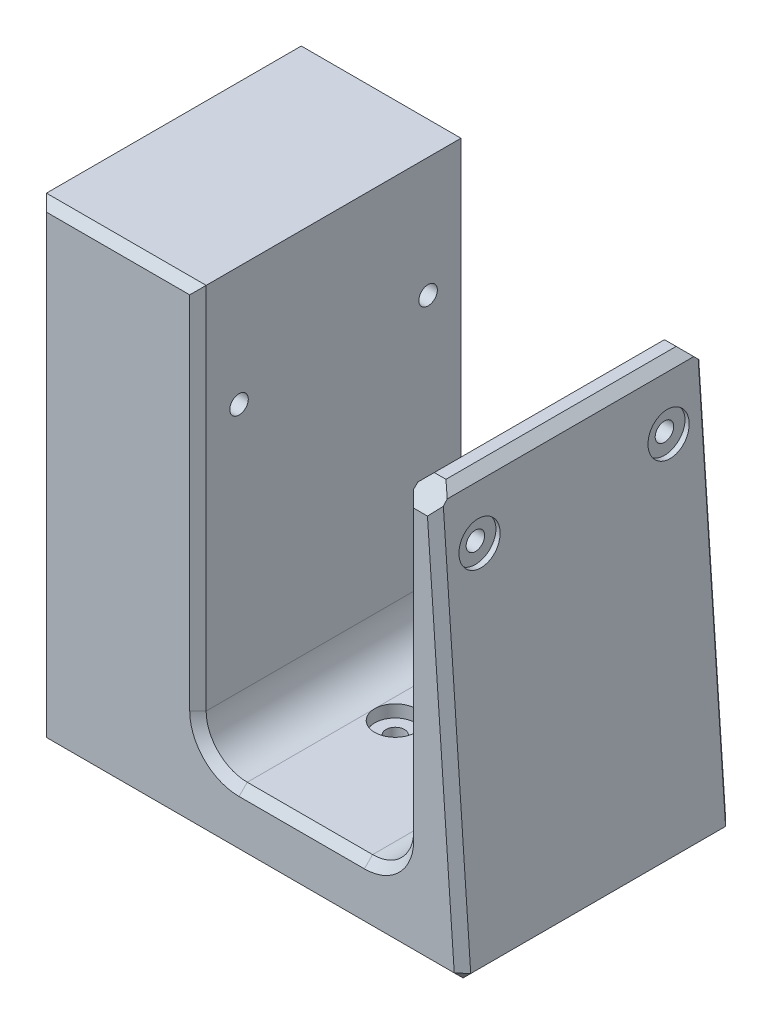
SolidWorks part; units mm, degrees
material "ABS generico"
ref_plane "Piano frontale" through (0, 0, 0) normal (0, 0, 1) x (1, 0, 0)
ref_plane "Piano superiore" through (0, 0, 0) normal (0, 1, 0) x (1, 0, 0)
ref_plane "Piano destro" through (0, 0, 0) normal (1, 0, 0) x (0, 0, -1)
sketch "Schizzo1" plane through (0, 0, 0) normal (0, 0, 1) x (1, 0, 0)
  line L0 (25.25, 100) -> (32.25, 100)
  line L1 (32.25, 100) -> (39.25, 0)
  line L2 (39.25, 0) -> (-39.25, 0)
  line L3 (-39.25, 0) -> (-32.25, 100) construction
  line L4 (-32.25, 100) -> (-25.25, 100) construction
  line L5 (-25.25, 100) -> (-25.25, 15)
  line L6 (-25.25, 15) -> (25.25, 15)
  line L7 (25.25, 15) -> (25.25, 100)
  line L8 (0, 15) -> (0, 0) construction
  line L9 (-25.25, 100) -> (-25.25, 114.69)
  line L10 (-25.25, 114.69) -> (-64.1103, 114.69)
  line L11 (-64.1103, 114.69) -> (-64.1103, 0)
  line L12 (-64.1103, 0) -> (-39.25, 0)
  point P2 (0, 0)
  point P12 (-91.5785, 119.1036)
  dimension "D1" = 7
  dimension "D2" = 50.5
  dimension "D3" = 14
  dimension "D4" = 100
  dimension "D5" = 85
  dimension "D6" = 38.8603
  dimension "D7" = 14.69
extrude "Estrusione-Estrusione1" add sketch "Schizzo1" along normal blind 66
fillet "Raccordo1" radius 10 2 edges at (-25.25, 15, 33) (25.25, 15, 33)
chamfer "Smusso1" distance 2 angle 45 21 edges at (32.25, 100, 33) (39.25, 0, 33) (25.25, 62.5, 66) (22.3211, 17.9289, 66) (0, 15, 66) (-22.3211, 17.9289, 66) (-25.25, 69.845, 66) (35.75, 50, 66) (-12.4302, 0, 66) (25.25, 62.5, 0) (22.3211, 17.9289, 0) (0, 15, 0) (-22.3211, 17.9289, 0) (-25.25, 69.845, 0) (-12.4302, 0, 0) (35.75, 50, 0) (25.25, 100, 33) (-64.1103, 57.345, 66) (-64.1103, 57.345, 0) (-44.6802, 114.69, 66) (-44.6802, 114.69, 0)
chamfer "Smusso2" distance 5 angle 45 2 edges at (28.6721, 100, 66) (28.6721, 100, 0)
ref_plane "Piano1" through (-35.25, 0, 0) normal (1, 0, 0) x (0, 0, -1)
ref_plane "Piano2" through (35.25, 0, 0) normal (-1, 0, 0) x (0, 0, 1)
sketch "Schizzo4" plane through (35.25, 0, 0) normal (-1, 0, 0) x (0, 0, 1)
  line L1 (56, 85.6136) -> (10, 85.6136) construction
  line L3 (2, 0) -> (64, 0) construction
  line L4 (66, 2) -> (66, 95) construction
  point P0 (56, 85.6136)
  point P2 (10, 85.6136)
  dimension "D1" = 85.6136
  dimension "D2" = 10
  dimension "D3" = 46
hole_wizard "Foro lamato per Vite M4 a testa cilindrica piana-2" positions "Schizzo4" profile "Schizzo5" counterbore size "M4" standard "ISO"
sketch "Schizzo5" plane through (35.25, 85.6136, 56) normal (0, 1, 0) x (0, 0, -1)
  line L0 (0, 0) -> (0, 31.3519)
  line L1 (0, 31.3519) -> (2.25, 30)
  line L2 (2.25, 30) -> (2.25, 3)
  line L3 (2.25, 3) -> (5, 3)
  line L4 (5, 3) -> (5, 0)
  line L5 (5, 0) -> (0, 0)
  line L10 (0, 31.3519) -> (-2.25, 30) construction
  line L11 (0, -6.35) -> (0, 107.95) construction
  dimension "Hole Dia." = 4.5
  dimension "Hole Depth" = 30
  dimension "C'Bore Dia." = 10
  dimension "C'Bore Depth" = 3
  dimension "Drill Angle" = 118
hole_wizard "Foro lamato per Vite M4 a testa cilindrica piana-3" positions "Schizzo6" profile "Schizzo7" counterbore size "M4" standard "ISO"
sketch "Schizzo6" plane through (0, 15, 0) normal (0, 1, 0) x (1, 0, 0)
  line L0 (-10.2456, -33) -> (9.7544, -33) construction
  line L2 (25.25, -2) -> (25.25, -64) construction
  line L3 (-15.25, 0) -> (15.25, 0) construction
  point P0 (-10.2456, -33)
  point P2 (9.7544, -33)
  dimension "D1" = 20
  dimension "D2" = 15.4956
  dimension "D3" = 33
sketch "Schizzo7" plane through (-10.2456, 15, 33) normal (1, 0, 0) x (0, 0, 1)
  line L0 (0, 0) -> (0, 31.3519)
  line L1 (0, 31.3519) -> (2.25, 30)
  line L2 (2.25, 30) -> (2.25, 3)
  line L3 (2.25, 3) -> (5, 3)
  line L4 (5, 3) -> (5, 0)
  line L5 (5, 0) -> (0, 0)
  line L10 (0, 31.3519) -> (-2.25, 30) construction
  line L11 (0, -6.35) -> (0, 107.95) construction
  dimension "Hole Dia." = 4.5
  dimension "Hole Depth" = 30
  dimension "C'Bore Dia." = 10
  dimension "C'Bore Depth" = 3
  dimension "Drill Angle" = 118
sketch "Schizzo8" plane through (-64.1103, 0, 0) normal (-1, 0, 0) x (0, 0, 1)
  line L0 (10, 85.6136) -> (56, 85.6136) construction
  line L2 (66, 112.69) -> (66, 2) construction
  line L3 (64, 0) -> (2, 0) construction
  point P0 (10, 85.6136)
  point P2 (56, 85.6136)
  dimension "D1" = 46
  dimension "D2" = 10
  dimension "D3" = 85.6136
hole_wizard "Foro lamato per Vite M4 a testa cilindrica piana-4" positions "Schizzo8" profile "Schizzo9" counterbore size "M4" standard "ISO"
sketch "Schizzo9" plane through (-64.1103, 85.6136, 10) normal (0, 1, 0) x (0, 0, 1)
  line L0 (0, 0) -> (0, 46.3519)
  line L1 (0, 46.3519) -> (2.25, 45)
  line L2 (2.25, 45) -> (2.25, 32)
  line L3 (2.25, 32) -> (5, 32)
  line L4 (5, 32) -> (5, 0)
  line L5 (5, 0) -> (0, 0)
  line L10 (0, 46.3519) -> (-2.25, 45) construction
  line L11 (0, -6.35) -> (0, 107.95) construction
  dimension "Hole Dia." = 4.5
  dimension "Hole Depth" = 45
  dimension "C'Bore Dia." = 10
  dimension "C'Bore Depth" = 32
  dimension "Drill Angle" = 118
